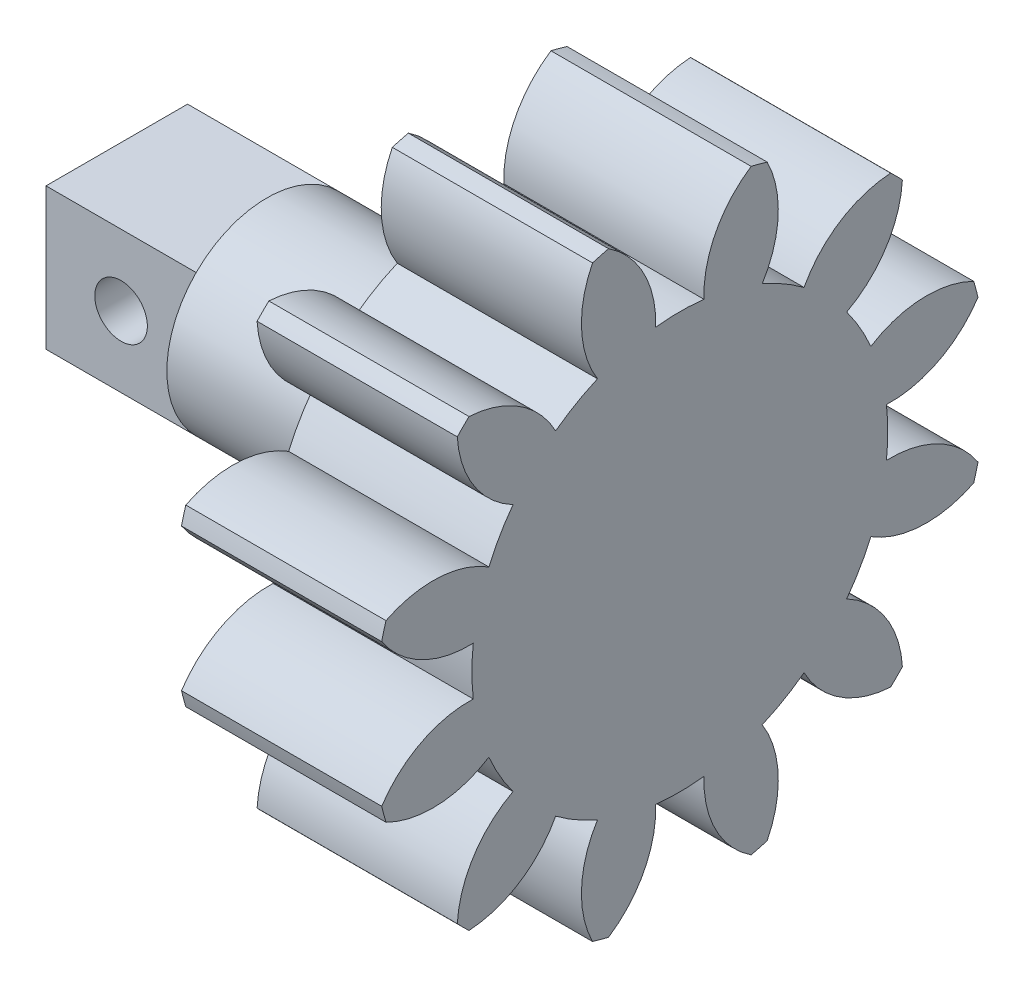
SolidWorks part; units mm, degrees
material "PLA personnalisé"
ref_plane "Plane1" through (0, 0, 0) normal (0, 0, 1) x (1, 0, 0)
ref_plane "Plane2" through (0, 0, 0) normal (0, 1, 0) x (1, 0, 0)
ref_plane "Plane3" through (0, 0, 0) normal (1, 0, 0) x (0, 0, -1)
other "Configuration Table"
sketch "HoldingSke" plane through (0, 0, 0) normal (0, 1, 0) x (1, 0, 0)
  line L0 (0, 0) -> (0.5589, -0.1188)
  line L1 (-15, 0) -> (100, 0) construction
  line L2 (0, 0) -> (-2.1039, 2.3779)
  line L3 (0, 0) -> (-11.863, 4.5341)
  line L4 (0, 0) -> (8.4473, 1.7955)
  line L5 (0, 0) -> (-46.8476, -17.4728)
  line L6 (0, 0) -> (-8.2896, -5.593)
  line L7 (-2.1039, 2.3779) -> (8.6586, 51.2059)
  line L8 (-76.2, 54.61) -> (-74.8, 54.61)
  line L9 (-71.009, 38.7566) -> (-53.1078, 45.2721)
  line L10 (-76.2, 71.12) -> (104.1128, 71.12)
  line L11 (0, 0) -> (-10, 0)
  line L12 (-76.2, 101.6) -> (-76.147, 101.6)
  line L13 (24.9733, 27.94) -> (52.9518, 28.4284)
  line L14 (24.9733, 27.94) -> (24.9743, 27.94)
  line L15 (24.9733, 27.94) -> (100.4006, 29.5858)
  line L16 (-63.627, -1.75) -> (-12.827, -1.75)
  circle A0 centre (0, 0) radius 4.5
  circle A1 centre (0, 0) radius 8.3115
  circle A2 centre (0, 0) radius 37.5
  circle A3 centre (0, 0) radius 4.5
  dimension "MHD" = 16.623
  dimension "Hub_dia" = 75
  dimension "Bore" = 9
  dimension "MBD" = 9
  dimension "Num_teeth" = 12
  dimension "Pitch" = 0.5714
  dimension "Overall_len" = 50
  dimension "Show_teeth" = 12
  dimension "Thickness" = 10
  dimension "OAL" = 50.0001
  dimension "T_dim" = 1.4
  dimension "Ap" = 20
  dimension "H" = 19.05
  dimension "Pitch_radius" = 180.3128
  dimension "Width" = 10
  dimension "Backlash" = 0.053
  dimension "Addendum_fac" = 1
  dimension "Dedendum_fac" = 1.25
  dimension "Clearance_fac" = 0.25
  dimension "Dedendum_add" = 0.001
  dimension "Module" = 1.75
sketch "BasProSke" plane through (0, 0, 0) normal (0, 1, 0) x (1, 0, 0)
  line L0 (-10, 0) -> (60, 0) construction
  line L1 (0, 0) -> (0, 12.25)
  line L2 (0, 0) -> (10, 0)
  line L3 (10, 0) -> (10, 12.25)
  line L4 (10, 12.25) -> (0, 12.25)
  dimension "Thickness" = 10
  dimension "Diameter" = 24.5
revolve "Base-Revolve" add sketch "BasProSke" angle 360 about L0
sketch "TooCutSke" plane through (0, 0, 0) normal (1, 0, 0) x (0, 0, -1)
  line L1 (0, 0) -> (0, 107) construction
  line L2 (0, 0) -> (-1.4632, 10.3976) construction
  line L3 (0, 0) -> (-5.3948, 20.1337) construction
  line L4 (-1.4632, 10.3976) -> (-2.6974, 10.0668) construction
  arc A0 (0.9651, 8.2553) -> (-0.9651, 8.2553) centre (0, 0) ccw
  arc A1 (2.8783, 11.9332) -> (-2.8783, 11.9332) centre (0, 0) ccw
  circle A2 centre (0, 0) radius 10.5 construction
  circle A3 centre (0, 0) radius 9.8668 construction
  arc A4 (-0.9651, 8.2553) -> (-2.8783, 11.9332) centre (-5.1623, 8.4085) ccw
  arc A5 (2.8783, 11.9332) -> (0.9651, 8.2553) centre (5.1623, 8.4085) ccw
  dimension "Root_dia" = 16.623
  dimension "Overcut_dia" = 24.5508
  dimension "Pitch_dia" = 21
  dimension "Base_dia" = 19.7335
  dimension "Flank_rad" = 4.2
  dimension "Half_ang" = 15
  dimension "Half_CT" = 1.2778
extrude "ToothCut" cut sketch "TooCutSke" along normal through all
fillet "Breaks" [suppressed] radius 0.035 tangent propagation no
fillet "RootFillets" [suppressed] radius 0.4385
pattern_circular "TeethCuts" count 12 every 30 about axis through (-10, 0, 0) along (1, 0, 0) of "ToothCut", "RootFillets", "Breaks"
sketch "HubNeaOneSke" plane through (0, 0, 0) normal (-1, 0, 0) x (0, 0, 1)
  circle A0 centre (0, 0) radius 8.3115
  dimension "Diameter" = 16.623
extrude "HubNearOne" [suppressed] add sketch "HubNeaOneSke" along normal blind 40.0001
sketch "HubNeaBotSke" plane through (0, 0, 0) normal (-1, 0, 0) x (0, 0, 1)
  circle A0 centre (0, 0) radius 8.3115
  dimension "Diameter" = 16.623
extrude "HubNearBoth" [suppressed] add sketch "HubNeaBotSke" along normal blind 20
ref_plane "FarPln" through (10, 0, 0) normal (1, 0, 0) x (0, 0, -1)
sketch "HubFarSke" plane through (10, 0, 0) normal (1, 0, 0) x (0, 0, -1)
  circle A0 centre (0, 0) radius 8.3115
  dimension "Diameter" = 16.623
extrude "HubFar" [suppressed] add sketch "HubFarSke" along normal blind 20
sketch "BorSke" plane through (0, 0, 0) normal (1, 0, 0) x (0, 0, -1)
  circle A0 centre (0, 0) radius 4.5
  dimension "Diameter" = 9
extrude "Bore" cut sketch "BorSke" along normal mid plane 100.0001
sketch "KeySke" plane through (0, 0, 0) normal (1, 0, 0) x (0, 0, -1)
  line L0 (-1.5, 0) -> (-1.5, 5.9)
  line L1 (-1.5, 5.9) -> (1.5, 5.9)
  line L2 (1.5, 5.9) -> (1.5, 0)
  line L3 (0, 0) -> (0, 34) construction
  line L4 (-1.5, 0) -> (1.5, 0)
  dimension "Offset" = 5.9
  dimension "Width" = 3
extrude "Keyway" [suppressed] cut sketch "KeySke" along normal mid plane 100.0001
pattern_circular "Keyway2" [suppressed] count 2 every 90 about axis through (-10, 0, 0) along (1, 0, 0) reverse direction yes
sketch "Esquisse4" plane through (0, 0, 0) normal (-1, 0, 0) x (0, 0, 1)
  circle A0 centre (0, 0) radius 16.8497
extrude "Enlèv. mat.-Extru.2" cut sketch "Esquisse4" against normal blind 2
sketch "Esquisse5" plane through (2, 0, 0) normal (-1, 0, 0) x (0, 0, 1)
  circle A0 centre (0, 0) radius 5.0708
extrude "Boss.-Extru.7" add sketch "Esquisse5" against normal blind 8
sketch "Esquisse6" plane through (2, 0, 0) normal (-1, 0, 0) x (0, 0, 1)
  circle A0 centre (0, 0) radius 4
  dimension "D1" = 8
extrude "Boss.-Extru.8" add sketch "Esquisse6" along normal blind 8.5
sketch "Esquisse7" plane through (-6.5, 0, 0) normal (-1, 0, 0) x (0, 0, 1)
  line L0 (4, 0) -> (-4, 0) construction
  line L1 (2.8284, -2.8284) -> (-2.8284, -2.8284)
  line L2 (2.8284, -2.8284) -> (2.8284, 2.8284)
  line L3 (2.8284, 2.8284) -> (-2.8284, 2.8284)
  line L4 (-2.8284, -2.8284) -> (-2.8284, 2.8284)
  line L5 (2.8284, -2.8284) -> (-2.8284, 2.8284) construction
  line L6 (2.8284, 2.8284) -> (-2.8284, -2.8284) construction
  line L7 (-4, 0) -> (0, 0) construction
  line L8 (0, 0) -> (0, 4) construction
  line L9 (0, 4) -> (0, 0) construction
  line L10 (0, 0) -> (3.4051, 3.4051) construction
  line L11 (3.4051, 3.4051) -> (0, 0) construction
  line L12 (0, 0) -> (-3.5303, 3.5303) construction
  circle A0 centre (0, 0) radius 4 construction
  circle A1 centre (0, 0) radius 4 construction
  point P0 (0, 0)
  dimension "D1" = 45
extrude "Boss.-Extru.9" add sketch "Esquisse7" along normal blind 6
sketch "Esquisse8" plane through (0, 0, -2.8284) normal (0, 0, -1) x (-1, 0, 0)
  line L0 (12.5, 0) -> (6.5, 0) construction
  line L1 (12.5, 2.8284) -> (12.5, -2.8284) construction
  line L2 (6.5, -2.8284) -> (6.5, 2.8284) construction
  circle A0 centre (9.5, 0) radius 1.05
  dimension "D1" = 2.1
extrude "Enlèv. mat.-Extru.3" cut sketch "Esquisse8" against normal blind 6
equation "' \"Module@HoldingSke\" = 6.35"
equation "' \"Num_teeth@HoldingSke\" = 12"
equation "' \"Ap@HoldingSke\" =  20"
equation "' \"Ap@HoldingSke\" = 20"
equation "' \"Width@HoldingSke\" = 0.5 * 25.4"
equation "' \"Hub_dia@HoldingSke\"= 1 * 25.4"
equation "' \"Hub_dia@HoldingSke\" = 1 * 25.4"
equation "' \"Overall_len@HoldingSke\" = 1.0 * 25.4"
equation "' \"Bore@HoldingSke\" = 0.75 * 25.4"
equation "' \"T_dim@HoldingSke\" = 0.1 * 25.4"
equation "' \"Width@KeySke\" = 0.25 * 25.4"
equation "' \"Show_teeth@HoldingSke\" = 13"
equation "' \"Backlash@HoldingSke\" = 0.009 * 25.4"
equation "' \"Addendum_fac@HoldingSke\" = 1.0"
equation "' \"Dedendum_fac@HoldingSke\" = 1.25"
equation "' \"Dedendum_add@HoldingSke\" = 0.00005 * 25.4"
equation "' \"Clearance_fac@HoldingSke\" = 0.25"
equation "\"Pitch@HoldingSke\" = 1 / \"Module@HoldingSke\""
equation "\"Overcut_dia@TooCutSke\" = (\"Num_teeth@HoldingSke\" + 2 * \"Addendum_fac@HoldingSke\") / \"Pitch@HoldingSke\" + 0.002 * 25.4"
equation "\"Pitch_dia@TooCutSke\" = \"Num_teeth@HoldingSke\" / \"Pitch@HoldingSke\""
equation "\"Base_dia@TooCutSke\" = \"Num_teeth@HoldingSke\" / \"Pitch@HoldingSke\" * cos((\"Ap@HoldingSke\"  * 3.14159265 / 180))"
equation "\"Root_dia@TooCutSke\" = (\"Num_teeth@HoldingSke\" + 2) / \"Pitch@HoldingSke\" - 2 * (\"Addendum_fac@HoldingSke\" + \"Dedendum_fac@HoldingSke\") / \"Pitch@HoldingSke\" - \"Dedendum_add@HoldingSke\" * 2"
equation "\"Half_ang@TooCutSke\" = 180 / \"Num_teeth@HoldingSke\""
equation "\"Half_CT@TooCutSke\" = \"Num_teeth@HoldingSke\" / \"Pitch@HoldingSke\" * sin((3.14159265 / 2 / \"Num_teeth@HoldingSke\")) / 2 - 7 * \"Backlash@HoldingSke\" / 4"
equation "\"Flank_rad@TooCutSke\" = \"Num_teeth@HoldingSke\" / \"Pitch@HoldingSke\" / 5"
equation "\"Radius@RootFillets\" = \"Clearance_fac@HoldingSke\" / \"Pitch@HoldingSke\" + \"Dedendum_add@HoldingSke\""
equation "\"Break_rad@Breaks\" = 0.02 / \"Pitch@HoldingSke\""
equation "\"Thickness@HoldingSke\" = \"Width@HoldingSke\""
equation "\"OAL@HoldingSke\" = \"Thickness@HoldingSke\""
equation "\"MHD@HoldingSke\" = (\"Num_teeth@HoldingSke\" + 2) / \"Pitch@HoldingSke\" - 2 * (\"Addendum_fac@HoldingSke\" + \"Dedendum_fac@HoldingSke\")  / \"Pitch@HoldingSke\" - \"Dedendum_add@HoldingSke\" * 2"
equation "\"MBD@HoldingSke\" = (\"Num_teeth@HoldingSke\" + 2) / \"Pitch@HoldingSke\" - 2 * (\"Addendum_fac@HoldingSke\" + \"Dedendum_fac@HoldingSke\")  / \"Pitch@HoldingSke\" - \"Dedendum_add@HoldingSke\" * 2 - 0.002 * 25.4"
equation "\"MHD@HoldingSke\" = ((sgn( \"MHD@HoldingSke\" - \"Hub_dia@HoldingSke\" )-1)*( \"MHD@HoldingSke\" - \"Hub_dia@HoldingSke\" ))/-2+ \"Hub_dia@HoldingSke\""
equation "\"MBD@HoldingSke\" = ((sgn( \"MBD@HoldingSke\" - \"Bore@HoldingSke\" )-1)*( \"MBD@HoldingSke\" - \"Bore@HoldingSke\" ))/-2+ \"Bore@HoldingSke\""
equation "\"OAL@HoldingSke\" = ((sgn( \"OAL@HoldingSke\" - \"Overall_len@HoldingSke\" )+1)*( \"OAL@HoldingSke\" - \"Overall_len@HoldingSke\" ))/2 + \"Overall_len@HoldingSke\" + 0.000002 * 25.4"
equation "\"Num_teeth@TeethCuts\" = int( \"Show_teeth@HoldingSke\" ) + 1"
equation "\"Num_teeth@TeethCuts\" = ((sgn( \"Num_teeth@TeethCuts\" - \"Num_teeth@HoldingSke\" )-1)*( \"Num_teeth@TeethCuts\" - \"Num_teeth@HoldingSke\" ))/-2+ \"Num_teeth@HoldingSke\""
equation "\"Num_teeth@TeethCuts\" = ((sgn( \"Num_teeth@TeethCuts\" - 2.0)+1)*( \"Num_teeth@TeethCuts\" - 2.0))/2 +2.0"
equation "\"Angle@TeethCuts\" = 360.0 / \"Num_teeth@HoldingSke\""
equation "\"Diameter@BasProSke\" = (\"Num_teeth@HoldingSke\" + 2 * \"Addendum_fac@HoldingSke\") / \"Pitch@HoldingSke\""
equation "\"Thickness@BasProSke\"  = \"Thickness@HoldingSke\""
equation "' \"Fillet_rad@BasProSke\" =  \"Thickness@HoldingSke\" * 0.05"
equation "' \"Fillet_rad@BasProSke\" = \"Thickness@HoldingSke\" * 0.05"
equation "\"MHD@HoldingSke\" = ((sgn( \"MHD@HoldingSke\" - \"Root_dia@TooCutSke\" )-1)*( \"MHD@HoldingSke\" - \"Root_dia@TooCutSke\" ))/-2+ \"Root_dia@TooCutSke\""
equation "\"Diameter@HubNeaOneSke\" = \"MHD@HoldingSke\""
equation "\"Length@HubNearOne\" = \"OAL@HoldingSke\" - \"Thickness@BasProSke\""
equation "\"Diameter@HubNeaBotSke\" = \"MHD@HoldingSke\""
equation "\"Length@HubNearBoth\" = ( \"OAL@HoldingSke\" - \"Thickness@BasProSke\" ) / 2.0"
equation "\"Thickness@FarPln\" = \"Thickness@BasProSke\""
equation "\"Diameter@HubFarSke\" = \"MHD@HoldingSke\""
equation "\"Length@HubFar\" = ( \"OAL@HoldingSke\" - \"Thickness@BasProSke\" ) / 2.0"
equation "\"Diameter@BorSke\" = \"MBD@HoldingSke\""
equation "\"D1@Bore\" = \"OAL@HoldingSke\" * 2.0"
equation "\"D1@Keyway\" = \"OAL@HoldingSke\" * 2.0"
equation "\"Offset@KeySke\" = \"T_dim@HoldingSke\" + \"MBD@HoldingSke\" / 2.0"
